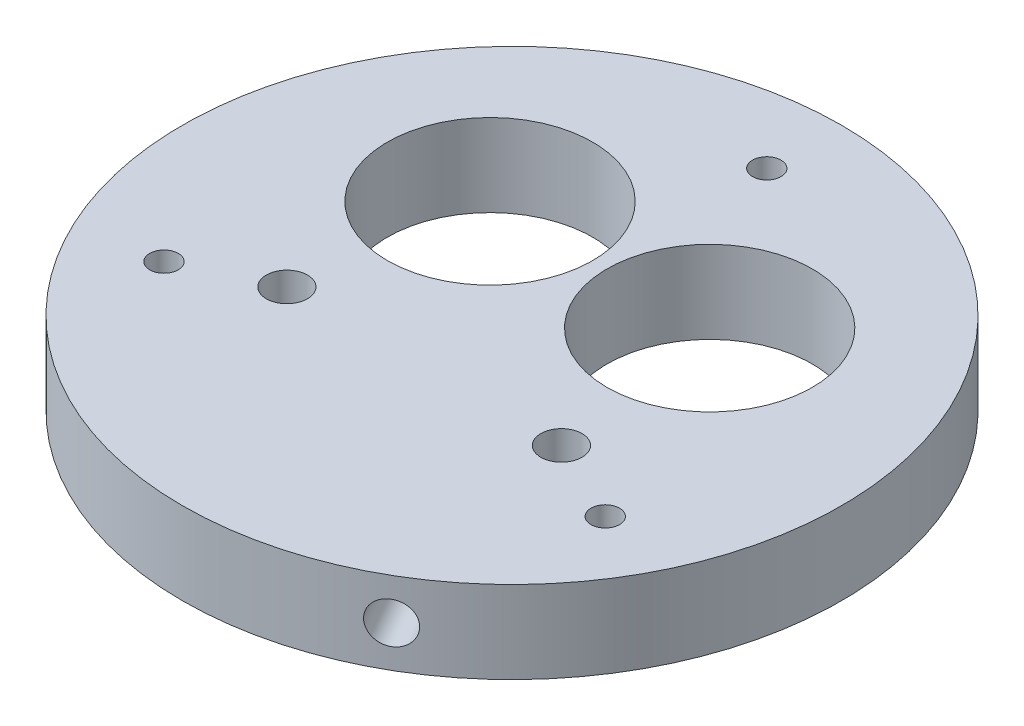
SolidWorks part; units mm, degrees
material "G10 Fiberglass"
ref_plane "Front Plane" through (0, 0, 0) normal (0, 0, 1) x (1, 0, 0)
ref_plane "Top Plane" through (0, 0, 0) normal (0, 1, 0) x (1, 0, 0)
ref_plane "Right Plane" through (0, 0, 0) normal (1, 0, 0) x (0, 0, -1)
sketch "Sketch1" plane through (0, 0, 0) normal (0, 1, 0) x (1, 0, 0)
  circle A0 centre (0, 0) radius 38.1127
  dimension "D1" = 76.2254
extrude "Boss-Extrude1" add sketch "Sketch1" along normal blind 9.525
sketch "Sketch2" plane through (0, 9.525, 0) normal (0, 1, 0) x (1, 0, 0)
  line L0 (12.7, 10.16) -> (-12.7, 10.16) construction
  line L3 (0, 6.35) -> (0, -19.05) construction
  line L4 (-14.6012, 35.2049) -> (-10.7695, 36.5595) construction
  line L5 (-14.6012, 35.2049) -> (-11.9555, 27.7213) construction
  line L6 (-10.7695, 36.5595) -> (-8.1239, 29.0759) construction
  line L7 (-11.9555, 27.7213) -> (-8.1239, 29.0759) construction
  line L8 (37.9022, -4.9723) -> (30.0984, -3.5218) construction
  line L9 (37.9022, -4.9723) -> (37.1595, -8.9679) construction
  line L10 (37.1595, -8.9679) -> (29.3557, -7.5173) construction
  line L11 (30.0984, -3.5218) -> (29.3557, -7.5173) construction
  line L12 (-23.144, -30.353) -> (-17.9858, -24.32) construction
  line L13 (-23.144, -30.353) -> (-26.2329, -27.712) construction
  line L14 (-26.2329, -27.712) -> (-21.0747, -21.679) construction
  line L15 (-17.9858, -24.32) -> (-21.0747, -21.679) construction
  line L16 (0, 10.16) -> (0, -18.415) construction
  line L17 (-12.7, 10.16) -> (12.7, 10.16) construction
  line L18 (-12.7, 24.13) -> (12.7, 24.13) construction
  line L19 (-12.7, -3.81) -> (12.7, -3.81) construction
  circle A0 centre (0, 0) radius 29.464 construction
  circle A1 centre (0, 29.464) radius 1.651
  circle A2 centre (25.5166, -14.732) radius 1.651
  circle A3 centre (-25.5166, -14.732) radius 1.651
  circle A4 centre (0, -18.415) radius 4.1275
  circle A7 centre (0, 0) radius 38.1127 construction
  circle A8 centre (-12.7, 10.16) radius 11.8745
  circle A9 centre (12.7, 10.16) radius 11.8745
  circle A10 centre (0, 20.32) radius 3.175
  circle A11 centre (0, 0) radius 3.175
  arc A12 (-12.7, 24.13) -> (-12.7, -3.81) centre (-12.7, 10.16) ccw construction
  arc A13 (12.7, -3.81) -> (12.7, 24.13) centre (12.7, 10.16) ccw construction
  point P11 (0, 0)
  point P36 (0.0524, -0.0401)
  point P38 (0, 10.16)
  dimension "D1" = 3.302
  dimension "D2" = 58.928
  dimension "D11" = 8.255
  dimension "D4" = 23.749
  dimension "D5" = 23.749
  dimension "D13" = 6.35
  dimension "D14" = 6.35
  dimension "D7" = 4.064
  dimension "D8" = 7.9375
  dimension "D6" = 10.16
  dimension "D10" = 25.4
  dimension "D12" = 28.575
  dimension "D15" = 27.94
  dimension "D17" = 3.81
  dimension "D16" = 3.81
  dimension "D3" = 3
  dimension "D9" = 3
extrude "Cut-Extrude1" cut sketch "Sketch2" against normal through all contours A1 | A3 | A8 | A9 | A2 region at (0, 9.525, -29.464) region at (25.5166, 9.525, 14.732) region at (-25.5166, 9.525, 14.732) region at (-12.7, 9.525, -10.16) region at (12.7, 9.525, -10.16)
ref_plane "Plane1" through (19.0563, 0, -33.0066) normal (0.5, 0, -0.866) x (0, -1, 0)
sketch "Sketch4" plane through (19.0563, 0, -33.0066) normal (0.5, 0, -0.866) x (0, -1, 0)
  circle A0 centre (-4.7625, 0) radius 2.3749
  dimension "D1" = 4.7625
  dimension "D2" = 4.7498
extrude "Cut-Extrude2" cut sketch "Sketch4" against normal blind 6.35
ref_axis "Axis1" through (0, 10.0012, 0) along (0, -1, 0)
pattern_circular "CirPattern1" count 3 over 360 about axis through (0, 10.0012, 0) along (0, -1, 0) of "Cut-Extrude2"
sketch "Sketch5" plane through (0, 9.525, 0) normal (0, 1, 0) x (1, 0, 0)
  line L0 (15.875, -10.16) -> (-15.875, -10.16) construction
  line L1 (0, 0) -> (0, -10.16) construction
  circle A0 centre (-15.875, -10.16) radius 2.3813
  circle A1 centre (15.875, -10.16) radius 2.3812
  dimension "D1" = 4.7625
  dimension "D2" = 4.7625
  dimension "D3" = 10.16
  dimension "D4" = 31.75
extrude "Cut-Extrude3" cut sketch "Sketch5" against normal through all both
equation "\"D5@Sketch2\"=\"D4@Sketch2\""
equation "\"D4@Sketch2\"=0.925in+0.01"
equation "\"D13@Sketch2\"=\"D14@Sketch2\""
equation "\"D16@Sketch2\"=\"D17@Sketch2\""
